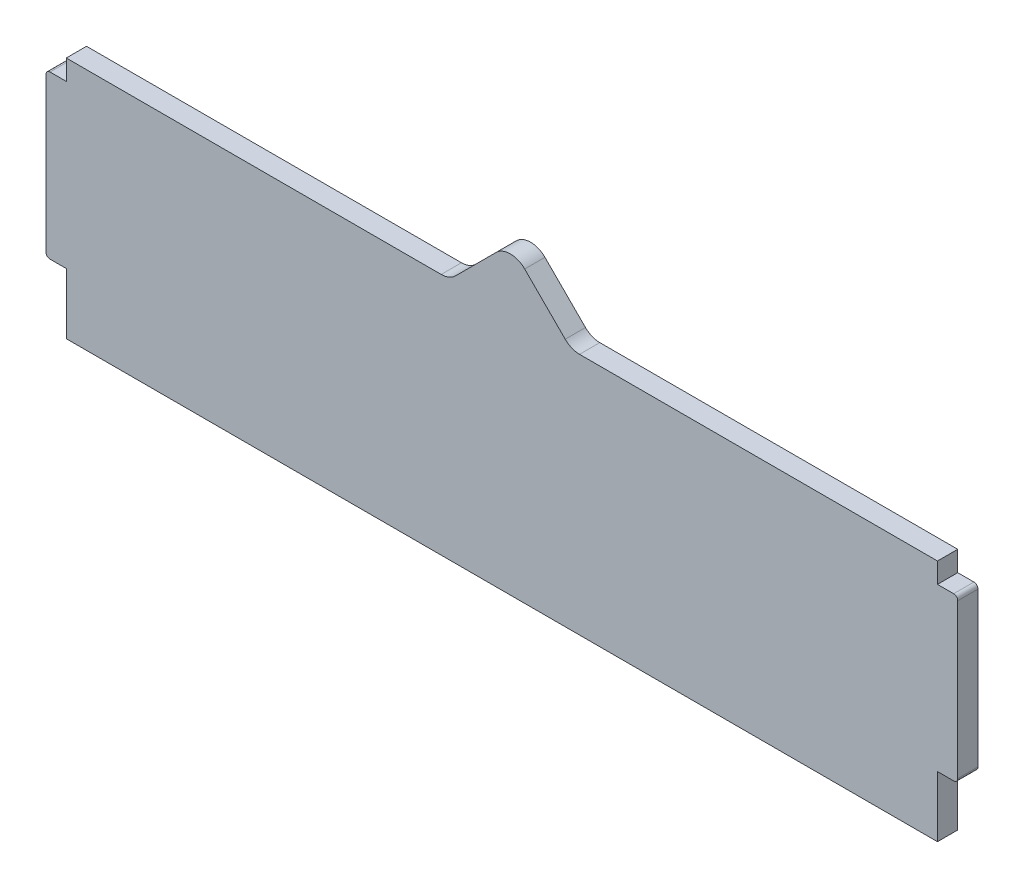
SolidWorks part; units mm, degrees
ref_plane "Front" through (0, 0, 0) normal (0, 0, 1) x (1, 0, 0)
ref_plane "Top" through (0, 0, 0) normal (0, 1, 0) x (1, 0, 0)
ref_plane "Right" through (0, 0, 0) normal (1, 0, 0) x (0, 0, -1)
sketch "Sketch1" plane through (0, 0, 0) normal (0, 0, 1) x (1, 0, 0)
  line L0 (215, 55) -> (215, 60)
  line L1 (0, 0) -> (215, 0)
  line L2 (0, 0) -> (0, 15)
  line L3 (0, 60) -> (94.5956, 60)
  line L4 (215, 0) -> (215, 15)
  line L5 (0, 55) -> (-5, 55)
  line L7 (0, 15) -> (-5, 15)
  line L8 (-5, 55) -> (-5, 15)
  line L9 (215, 55) -> (220, 55)
  line L11 (215, 15) -> (220, 15)
  line L12 (220, 55) -> (220, 15)
  line L13 (0, 55) -> (0, 60)
  line L14 (94.5956, 60) -> (109.5956, 75)
  line L15 (109.5956, 75) -> (124.5956, 60)
  line L16 (124.5956, 60) -> (215, 60)
  dimension "D1" = 215
  dimension "D2" = 60
  dimension "D3" = 5
  dimension "D4" = 5
  dimension "D5" = 40
  dimension "D6" = 5
  dimension "D7" = 40
  dimension "D8" = 5
  dimension "D9" = 15
  dimension "D10" = 15
extrude "Boss-Extrude1" add sketch "Sketch1" along normal blind 5
fillet "Fillet1" radius 5 3 edges at (94.5956, 60, 2.5) (124.5956, 60, 2.5) (109.5956, 75, 2.5)
fillet "Fillet2" radius 1 4 edges at (-5, 55, 2.5) (-5, 15, 2.5) (220, 15, 2.5) (220, 55, 2.5)
